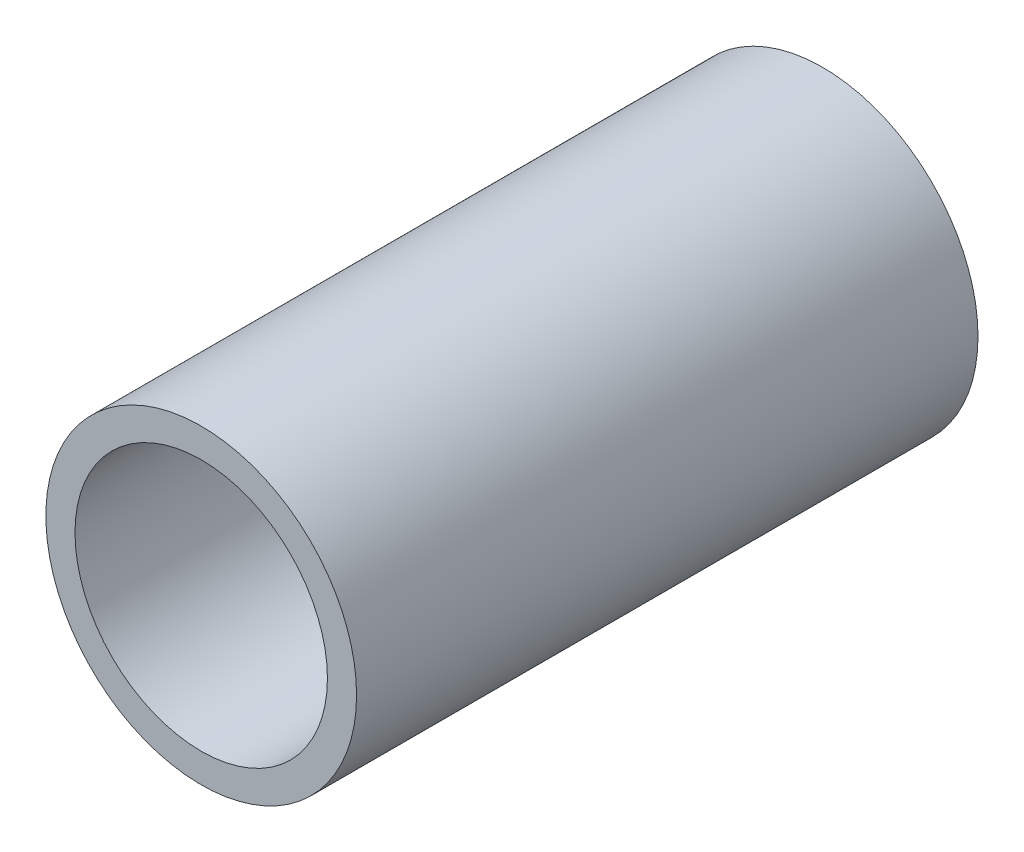
SolidWorks part; units mm, degrees
ref_plane "Plan de face" through (0, 0, 0) normal (0, 0, 1) x (1, 0, 0)
ref_plane "Plan de dessus" through (0, 0, 0) normal (0, 1, 0) x (1, 0, 0)
ref_plane "Plan de droite" through (0, 0, 0) normal (1, 0, 0) x (0, 0, -1)
sketch "Sketch1" plane through (0, 0, 0) normal (0, 0, 1) x (1, 0, 0)
  circle A0 centre (0, 0) radius 4
  circle A1 centre (0, 0) radius 3.25
  dimension "D1" = 8
  dimension "D2" = 6.5
extrude "Boss-Extrude1" add sketch "Sketch1" along normal blind 16
